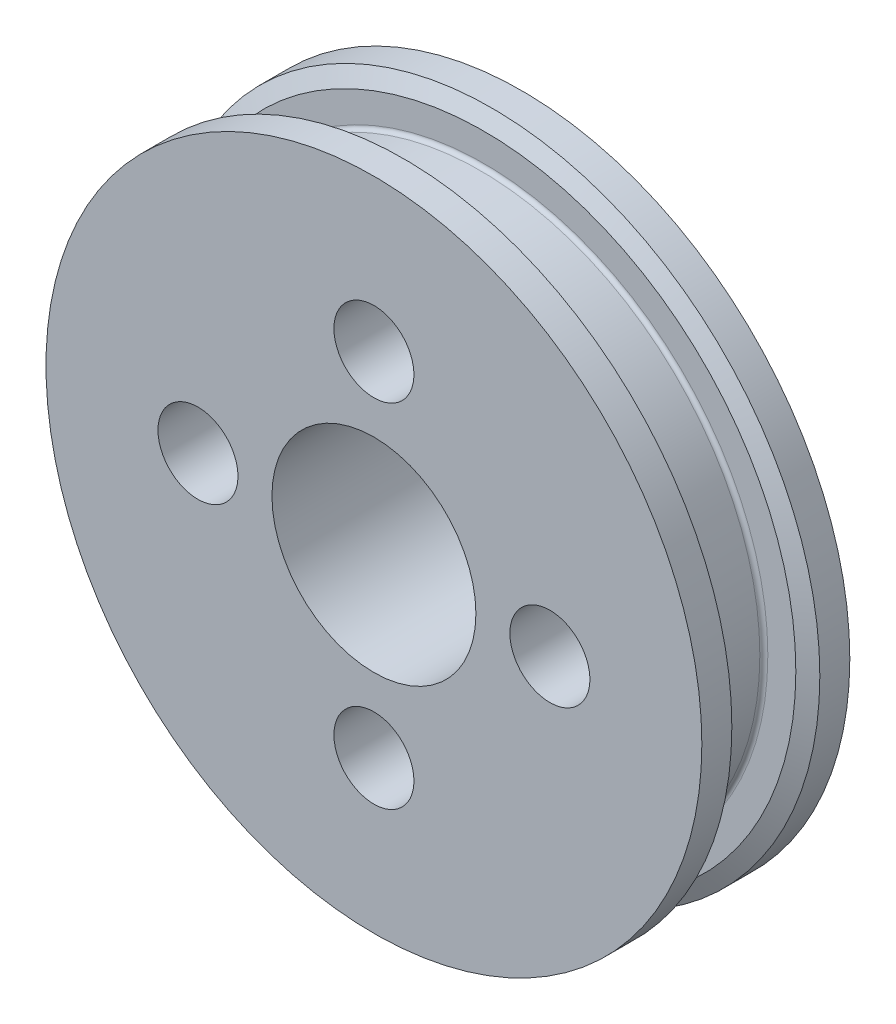
SolidWorks part; units mm, degrees
ref_plane "Front Plane" through (0, 0, 0) normal (0, 0, 1) x (1, 0, 0)
ref_plane "Top Plane" through (0, 0, 0) normal (0, 1, 0) x (1, 0, 0)
ref_plane "Right Plane" through (0, 0, 0) normal (1, 0, 0) x (0, 0, -1)
sketch "Sketch2" plane through (0, 0, 0) normal (1, 0, 0) x (0, 0, -1)
  line L0 (0, 6.477) -> (0, 20.828)
  line L1 (0, 20.828) -> (1.905, 20.828)
  line L2 (2.413, 19.812) -> (2.413, 17.78)
  line L3 (2.413, 17.78) -> (6.985, 17.78)
  line L4 (6.985, 17.78) -> (6.985, 19.812)
  line L5 (7.493, 20.828) -> (9.398, 20.828)
  line L6 (9.398, 20.828) -> (9.398, 6.477)
  line L8 (0, 6.477) -> (9.398, 6.477)
  line L9 (0, 6.477) -> (0, 0) construction
  line L10 (0, 0) -> (10.7816, 0) construction
  line L11 (6.985, 19.812) -> (7.493, 20.828)
  line L12 (1.905, 20.828) -> (2.413, 19.812)
  point P4 (2.413, 20.828)
  point P7 (6.985, 20.828)
  dimension "D1" = 17.78
  dimension "D2" = 9.398
  dimension "D3" = 3.048
  dimension "D4" = 6.477
  dimension "D5" = 4.572
  dimension "D6" = 1.016
  dimension "D7" = 0.508
  dimension "D8" = 0.508
  dimension "D9" = 1.016
revolve "Revolve1" add sketch "Sketch2" angle 360 about L10
sketch "Sketch3" plane through (0, 0, -9.398) normal (0, 0, -1) x (-1, 0, 0)
  line L1 (-8.255, -8.255) -> (8.255, -8.255)
  line L2 (-8.255, -8.255) -> (-8.255, 8.255)
  line L3 (-8.255, 8.255) -> (8.255, 8.255)
  line L4 (8.255, -8.255) -> (8.255, 8.255)
  circle A0 centre (0, 0) radius 6.477 construction
  circle A1 centre (0, 0) radius 6.477
  point P4 (8.255, 0)
  point P6 (0, 8.255)
  dimension "D1" = 16.51
extrude "Boss-Extrude1" add sketch "Sketch3" along normal blind 3.175
ref_plane "Plane1" through (0, 0, -4.699) normal (0, 0, -1) x (-1, 0, 0)
sketch "Sketch4" plane through (0, 0, -9.398) normal (0, 0, -1) x (-1, 0, 0)
  line L0 (0, 11.176) -> (0, 0) construction
  line L1 (0, 0) -> (0, -11.176) construction
  line L2 (-11.176, 0) -> (0, 0) construction
  line L3 (0, 0) -> (11.176, 0) construction
  circle A0 centre (0, 11.176) radius 2.54
  circle A1 centre (11.176, 0) radius 2.54
  circle A2 centre (0, -11.176) radius 2.54
  circle A3 centre (-11.176, 0) radius 2.54
  dimension "D1" = 5.08
  dimension "D2" = 11.176
extrude "Cut-Extrude1" cut sketch "Sketch4" against normal through all both and the other way through all
fillet "Fillet1" radius 0.254 2 edges at (17.78, 0, -6.985) (17.78, 0, -2.413)
